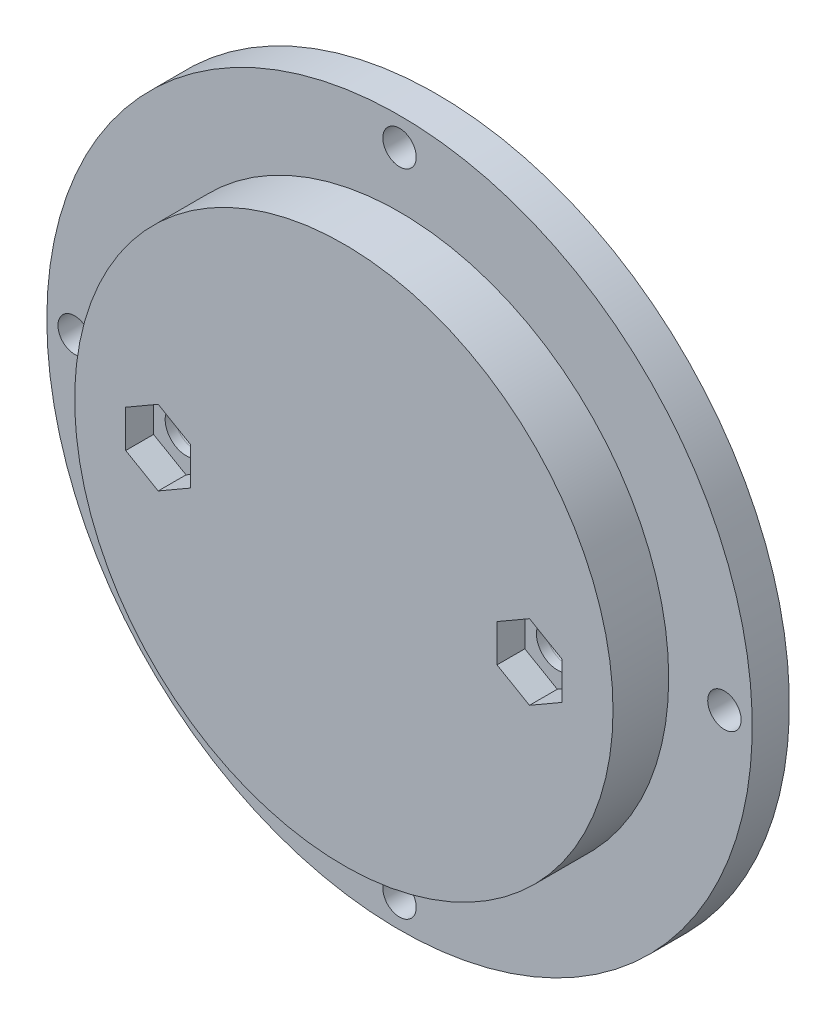
SolidWorks part; units mm, degrees
material "ｽﾃﾝﾚｽ鋼(鋳造)"
ref_plane "正面" through (0, 0, 0) normal (0, 0, 1) x (1, 0, 0)
ref_plane "平面" through (0, 0, 0) normal (0, 1, 0) x (1, 0, 0)
ref_plane "右側面" through (0, 0, 0) normal (1, 0, 0) x (0, 0, -1)
sketch "ｽｹｯﾁ1" plane through (0, 0, 0) normal (0, 1, 0) x (1, 0, 0)
  line L0 (0, 1.7) -> (0, 19.9)
  line L1 (0, 1.7) -> (0, 0) construction
  arc A0 (0, 19.9) -> (0, 1.7) centre (0, 10.8) cw
  dimension "D1" = 9.1
  dimension "D2" = 19.9
revolve "回転1" add sketch "ｽｹｯﾁ1" angle 360 about L0
sketch "ｽｹｯﾁ2" plane through (0, 0, 0) normal (0, 0, 1) x (1, 0, 0)
  line L0 (20, 0) -> (-20, 0) construction
  line L1 (-26, 0) -> (-20, 0) construction
  line L2 (-24.0086, 1.5704) -> (-9.9696, 12.6419)
  line L3 (-24.0086, -1.5704) -> (-9.9696, -12.6419)
  line L4 (0, -5.005) -> (0, 5.005) construction
  line L5 (24.0086, -1.5704) -> (9.9696, -12.6419)
  line L6 (24.0086, 1.5704) -> (9.9696, 12.6419)
  circle A0 centre (-20, 0) radius 2.25
  circle A1 centre (20, 0) radius 2.25
  arc A2 (-9.9696, -12.6419) -> (9.9696, -12.6419) centre (0, 0) ccw
  arc A3 (9.9696, 12.6419) -> (-9.9696, 12.6419) centre (0, 0) ccw
  arc A4 (24.0086, -1.5704) -> (24.0086, 1.5704) centre (22.7702, 0) ccw
  arc A5 (-24.0086, 1.5704) -> (-24.0086, -1.5704) centre (-22.7702, 0) ccw
  point P4 (0, 0)
  point P21 (26, 0)
  dimension "D2" = 4.5
  dimension "D3" = 32.2
  dimension "D4" = 2
  dimension "D1" = 40
  dimension "D5" = 26
extrude "ﾎﾞｽ - 押し出し1" add sketch "ｽｹｯﾁ2" against normal blind 1 separate body
sketch "ｽｹｯﾁ3" plane through (0, 0, -1) normal (0, 0, -1) x (-1, 0, 0)
  circle A0 centre (0, 0) radius 14.1
  arc A1 (-9.9696, -12.6419) -> (9.9696, -12.6419) centre (0, 0) ccw construction
  dimension "D1" = 2
extrude "ﾎﾞｽ - 押し出し2" add sketch "ｽｹｯﾁ3" along normal blind 14.35
fillet "ﾌｨﾚｯﾄ1" radius 4 1 edges at (-14.1, 0, -15.35)
fillet "ﾌｨﾚｯﾄ2" radius 2 1 edges at (-14.1, 0, -1)
sketch "ｽｹｯﾁ4" plane through (0, 0, 0) normal (1, 0, 0) x (0, 0, -1)
  line L0 (0, 0) -> (19.9, 0)
  arc A0 (15.35, -7.8808) -> (15.35, 7.8808) centre (10.8, 0) ccw construction
sketch "ｽｹｯﾁ5" plane through (0, 0, 0) normal (0, 0, 1) x (1, 0, 0)
  line L8 (-10.8985, 13.8197) -> (-24.9375, 2.7482)
  line L9 (-24.9375, -2.7482) -> (-10.8985, -13.8197)
  line L10 (10.8985, -13.8197) -> (24.9375, -2.7482)
  line L11 (24.9375, 2.7482) -> (10.8985, 13.8197)
  line L12 (-10.8985, 13.8197) -> (-24.9375, 2.7482)
  line L13 (-24.9375, -2.7482) -> (-10.8985, -13.8197)
  line L14 (10.8985, -13.8197) -> (24.9375, -2.7482)
  line L15 (24.9375, 2.7482) -> (10.8985, 13.8197)
  circle A4 centre (0, 0) radius 29
  arc A8 (10.8985, 13.8197) -> (-10.8985, 13.8197) centre (0, 0) ccw
  arc A9 (-24.9375, 2.7482) -> (-24.9375, -2.7482) centre (-22.7702, 0) ccw
  arc A10 (-10.8985, -13.8197) -> (10.8985, -13.8197) centre (0, 0) ccw
  arc A11 (24.9375, -2.7482) -> (24.9375, 2.7482) centre (22.7702, 0) ccw
  arc A12 (10.8985, 13.8197) -> (-10.8985, 13.8197) centre (0, 0) ccw
  arc A13 (-24.9375, 2.7482) -> (-24.9375, -2.7482) centre (-22.7702, 0) ccw
  arc A14 (-10.8985, -13.8197) -> (10.8985, -13.8197) centre (0, 0) ccw
  arc A15 (24.9375, -2.7482) -> (24.9375, 2.7482) centre (22.7702, 0) ccw
  dimension "D2" = 58
  dimension "D1" = 1.5
extrude "ﾎﾞｽ - 押し出し3" add sketch "ｽｹｯﾁ5" against normal blind 6 separate body
sketch "ｽｹｯﾁ6" plane through (0, 0, 0) normal (0, 0, 1) x (1, 0, 0)
  circle A0 centre (20, 0) radius 2.25 construction
  circle A1 centre (20, 0) radius 2.25
  circle A2 centre (-20, 0) radius 2.25 construction
  circle A3 centre (-20, 0) radius 2.25
  circle A5 centre (0, 0) radius 29
  circle A6 centre (0, 0) radius 29
  dimension "D1" = 0
extrude "ﾎﾞｽ - 押し出し4" add sketch "ｽｹｯﾁ6" along normal blind 4
sketch "ｽｹｯﾁ7" plane through (0, 0, -6) normal (0, 0, -1) x (-1, 0, 0)
  circle A0 centre (0, 0) radius 35 construction
  circle A1 centre (0, 0) radius 38
  circle A2 centre (0, 35) radius 1.8
  circle A3 centre (35, 0) radius 1.8
  circle A4 centre (0, -35) radius 1.8
  circle A5 centre (-35, 0) radius 1.8
  circle A7 centre (0, 0) radius 29
  circle A8 centre (0, 0) radius 29
  point P6 (-41.503, 0)
  point P7 (0, 0)
  point P15 (0, 0)
  dimension "D1" = 70
  dimension "D2" = 76
  dimension "D3" = 3.6
  dimension "D5" = 0
  dimension "D4" = 4
extrude "ﾎﾞｽ - 押し出し5" add sketch "ｽｹｯﾁ7" against normal blind 4
sketch "ｽｹｯﾁ8" plane through (0, 0, 4) normal (0, 0, 1) x (1, 0, 0)
  line L1 (-20, 4.0415) -> (-23.5, 2.0207)
  line L2 (-23.5, 2.0207) -> (-23.5, -2.0207)
  line L3 (-23.5, -2.0207) -> (-20, -4.0415)
  line L4 (-20, -4.0415) -> (-16.5, -2.0207)
  line L5 (-16.5, -2.0207) -> (-16.5, 2.0207)
  line L6 (-16.5, 2.0207) -> (-20, 4.0415)
  line L7 (20, 4.0415) -> (16.5, 2.0207)
  line L8 (16.5, 2.0207) -> (16.5, -2.0207)
  line L9 (16.5, -2.0207) -> (20, -4.0415)
  line L10 (20, -4.0415) -> (23.5, -2.0207)
  line L11 (23.5, -2.0207) -> (23.5, 2.0207)
  line L12 (23.5, 2.0207) -> (20, 4.0415)
  circle A0 centre (-20, 0) radius 3.5 construction
  circle A1 centre (20, 0) radius 3.5 construction
  dimension "D1" = 7
extrude "ｶｯﾄ - 押し出し1" cut sketch "ｽｹｯﾁ8" against normal blind 3
